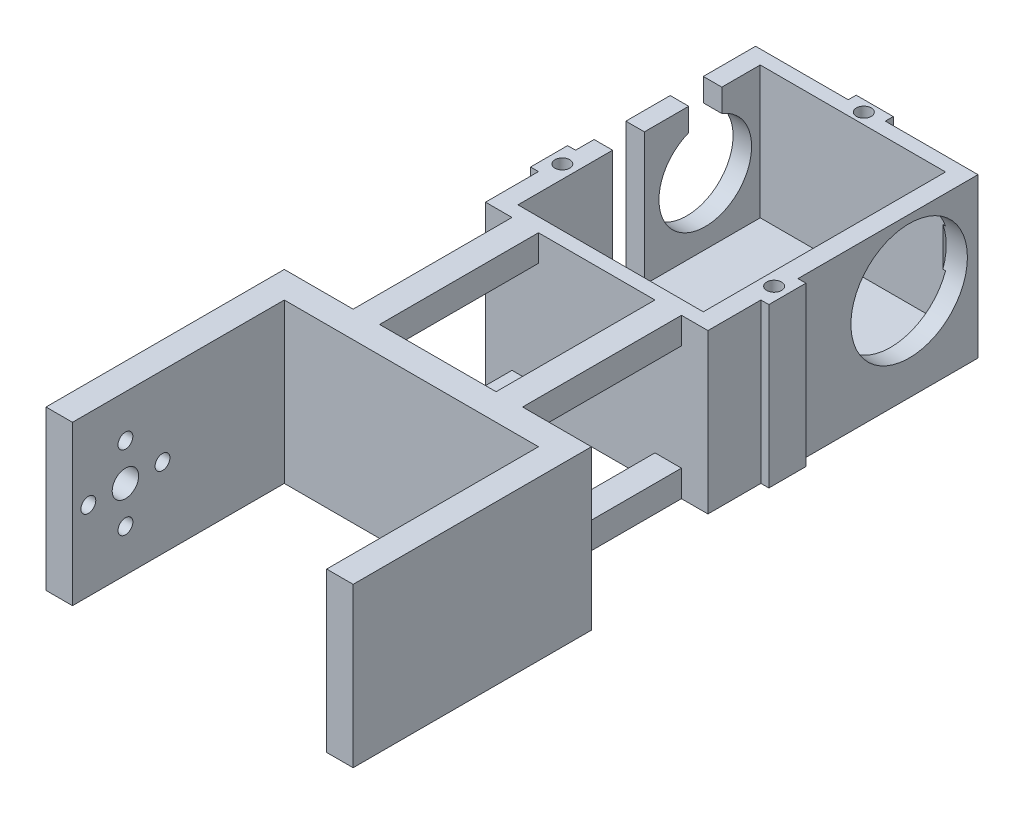
SolidWorks part; units mm, degrees
ref_plane "Front Plane" through (0, 0, 0) normal (0, 0, 1) x (1, 0, 0)
ref_plane "Top Plane" through (0, 0, 0) normal (0, 1, 0) x (1, 0, 0)
ref_plane "Right Plane" through (0, 0, 0) normal (1, 0, 0) x (0, 0, -1)
sketch "Sketch1" plane through (0, 0, 0) normal (0, 1, 0) x (1, 0, 0)
  line L1 (-21, 25.5) -> (21, 25.5)
  line L2 (-21, 25.5) -> (-21, -25.5)
  line L3 (-21, -25.5) -> (21, -25.5)
  line L4 (21, 25.5) -> (21, -25.5)
  line L5 (-11, -25.5) -> (-16, -25.5)
  line L6 (-11, -25.5) -> (-11, -55.5)
  line L7 (-11, -55.5) -> (-16, -55.5)
  line L8 (-16, -25.5) -> (-16, -55.5)
  line L9 (16, -25.5) -> (11, -25.5)
  line L10 (16, -25.5) -> (16, -55.5)
  line L11 (16, -55.5) -> (11, -55.5)
  line L12 (11, -25.5) -> (11, -55.5)
  line L13 (-29, -55.5) -> (29, -55.5)
  line L14 (-29, -55.5) -> (-29, -60.5)
  line L15 (-29, -60.5) -> (29, -60.5)
  line L16 (29, -55.5) -> (29, -60.5)
  line L17 (-24, -60.5) -> (-29, -60.5)
  line L18 (-24, -60.5) -> (-24, -100.5)
  line L19 (-24, -100.5) -> (-29, -100.5)
  line L20 (-29, -60.5) -> (-29, -100.5)
  line L21 (29, -60.5) -> (24, -60.5)
  line L22 (29, -60.5) -> (29, -100.5)
  line L23 (29, -100.5) -> (24, -100.5)
  line L24 (24, -60.5) -> (24, -100.5)
  point P4 (-21, 0)
  point P6 (0, 25.5)
  point P12 (0, -25.5)
  point P21 (0, -55.5)
  dimension "D1" = 42
  dimension "D2" = 51
  dimension "D3" = 5
  dimension "D4" = 30
  dimension "D5" = 5
  dimension "D6" = 5
  dimension "D7" = 5
  dimension "D8" = 58
  dimension "D9" = 40
extrude "Boss-Extrude1" add sketch "Sketch1" along normal blind 5 contours L4 L1 L2 L3 region at (0, 0, 0)
sketch "Sketch3" plane through (0, 5, 0) normal (0, 1, 0) x (1, 0, 0)
  line L1 (-17.5, 22.875) -> (17.5, 22.875)
  line L2 (-17.5, 22.875) -> (-17.5, -22.875)
  line L3 (-17.5, -22.875) -> (17.5, -22.875)
  line L4 (17.5, 22.875) -> (17.5, -22.875)
  line L5 (-21, 25.5) -> (21, 25.5)
  line L6 (-21, 25.5) -> (-21, -25.5)
  line L7 (-21, -25.5) -> (21, -25.5)
  line L8 (21, 25.5) -> (21, -25.5)
  point P4 (-17.5, 0)
  point P6 (0, 22.875)
  dimension "D1" = 35
  dimension "D2" = 45.75
extrude "Boss-Extrude3" add sketch "Sketch3" along normal blind 25
sketch "Sketch4" plane through (-21, 0, 0) normal (-1, 0, 0) x (0, 0, 1)
  line L1 (-25.5, 30) -> (25.5, 30) construction
  line L2 (0, 30) -> (0, 0) construction
  circle A0 centre (-12.5, 17.5) radius 8.75
  dimension "D2" = 17.5
  dimension "D1" = 12.5
  dimension "D3" = 12.5
extrude "Cut-Extrude2" cut sketch "Sketch4" against normal blind 5
sketch "Sketch6" plane through (-17.5, 0, 0) normal (1, 0, 0) x (0, 0, -1)
  line L0 (-25.5, 30) -> (25.5, 30) construction
  line L2 (0, 30) -> (0, 0) construction
  line L4 (9.375, 17.5) -> (9.375, 30)
  line L5 (9.375, 30) -> (15.625, 30)
  line L6 (15.625, 17.5) -> (15.625, 30)
  line L7 (25.5, 0) -> (-25.5, 0) construction
  arc A0 (9.375, 17.5) -> (15.625, 17.5) centre (12.5, 17.5) ccw
  point P11 (12.5, 30)
  dimension "D1" = 6.25
  dimension "D2" = 12.5
  dimension "D3" = 12.5
extrude "Cut-Extrude3" cut sketch "Sketch6" against normal blind 4
sketch "Sketch7" plane through (-21, 0, 0) normal (-1, 0, 0) x (0, 0, 1)
  line L0 (-9.375, 30) -> (25.5, 30) construction
  line L1 (-1, 30) -> (5, 30)
  line L2 (-1, 30) -> (-1, 5)
  line L3 (-1, 5) -> (5, 5)
  line L4 (5, 30) -> (5, 5)
  line L6 (25.5, 30) -> (25.5, 0) construction
  line L7 (-25.5, 0) -> (25.5, 0) construction
  dimension "D1" = 20.5
  dimension "D2" = 5
  dimension "D3" = 6
extrude "Cut-Extrude4" cut sketch "Sketch7" against normal blind 4
sketch "Sketch9" plane through (21, 0, 0) normal (1, 0, 0) x (0, 0, -1)
  line L0 (25.5, 30) -> (25.5, 0) construction
  line L1 (-25.5, 30) -> (25.5, 30) construction
  circle A0 centre (12.5, 17.5) radius 11
  dimension "D2" = 22
  dimension "D1" = 13
  dimension "D3" = 12.5
extrude "Cut-Extrude5" cut sketch "Sketch9" against normal blind 4
sketch "Sketch16" plane through (-21, 0, 0) normal (-1, 0, 0) x (0, 0, 1)
  line L0 (5, 30) -> (25.5, 30) construction
  line L1 (15.5, 30) -> (8.5, 30)
  line L2 (15.5, 30) -> (15.5, 0)
  line L3 (15.5, 0) -> (8.5, 0)
  line L4 (8.5, 30) -> (8.5, 0)
  line L5 (-25.5, 0) -> (25.5, 0) construction
  line L6 (25.5, 30) -> (25.5, 0) construction
  dimension "D1" = 10
  dimension "D2" = 7
extrude "Boss-Extrude5" add sketch "Sketch16" along normal blind 1.5
sketch "Sketch17" plane through (21, 0, 0) normal (1, 0, 0) x (0, 0, -1)
  line L0 (-25.5, 30) -> (25.5, 30) construction
  line L1 (-15.5, 30) -> (-8.5, 30)
  line L2 (-15.5, 30) -> (-15.5, 0)
  line L3 (-15.5, 0) -> (-8.5, 0)
  line L4 (-8.5, 30) -> (-8.5, 0)
  line L5 (25.5, 0) -> (-25.5, 0) construction
  line L6 (-25.5, 30) -> (-25.5, 0) construction
  dimension "D1" = 10
  dimension "D2" = 7
extrude "Boss-Extrude6" add sketch "Sketch17" along normal blind 1.5
sketch "Sketch19" plane through (0, 0, -25.5) normal (0, 0, -1) x (-1, 0, 0)
  line L0 (-21, 30) -> (21, 30) construction
  line L1 (3.5, 30) -> (-3.5, 30)
  line L2 (3.5, 30) -> (3.5, 0)
  line L3 (3.5, 0) -> (-3.5, 0)
  line L4 (-3.5, 30) -> (-3.5, 0)
  line L5 (21, 0) -> (-21, 0) construction
  point P8 (0, 0)
  point P9 (0, 30)
  dimension "D1" = 7
extrude "Boss-Extrude7" add sketch "Sketch19" along normal blind 1.5
sketch "Sketch18" plane through (0, 30, 0) normal (0, 1, 0) x (1, 0, 0)
  line L0 (-22.5, -15.5) -> (-22.5, -8.5) construction
  line L1 (0, -19.5533) -> (0, 11.7982) construction
  line L2 (-3.5, 27) -> (3.5, 27) construction
  line L3 (-22.5, -12) -> (-17.5, -12) construction
  line L4 (-17.5, -5) -> (-17.5, -22.875) construction
  line L5 (0, 27) -> (0, 22.875) construction
  line L6 (17.5, 22.875) -> (-17.5, 22.875) construction
  circle A0 centre (-20, -12) radius 1.4
  circle A1 centre (20, -12) radius 1.4
  circle A2 centre (0, 24.9375) radius 1.4
  point P5 (-22.5, -12)
  point P17 (0, 27)
  point P21 (-20, -12)
  point P26 (0, 24.9375)
  dimension "D1" = 2.8
extrude "Cut-Extrude7" cut sketch "Sketch18" against normal blind 6
extrude "Boss-Extrude8" add sketch "Sketch1<3>" along normal blind 30 contours L3 L8 L7 L6 | L3 L12 L11 L10 | L16 L13 L11 L7 L14 L15 | L15 L24 L23 L22 | L15 L20 L19 L18
sketch "Sketch1<3>" plane through (0, 0, 0) normal (0, 1, 0) x (1, 0, 0) same geometry as "Sketch1"
sketch "Sketch21" plane through (24, 0, 0) normal (-1, 0, 0) x (0, 0, 1)
  line L0 (100.5, 30) -> (100.5, 0) construction
  circle A0 centre (90.5, 15) radius 2.95
  point P6 (100.5, 15)
  dimension "D1" = 5.9
  dimension "D2" = 10
extrude "Boss-Extrude9" add sketch "Sketch21" along normal blind 4
sketch "Sketch24" plane through (-16, 0, 0) normal (-1, 0, 0) x (0, 0, 1)
  line L0 (25.5, 30) -> (25.5, 0) construction
  line L1 (25.5, 25) -> (55.5, 25)
  line L2 (25.5, 25) -> (25.5, 5)
  line L3 (25.5, 5) -> (55.5, 5)
  line L4 (55.5, 25) -> (55.5, 5)
  line L5 (55.5, 30) -> (55.5, 0) construction
  point P8 (25.5, 15)
  point P9 (25.5, 15)
  dimension "D1" = 20
extrude "Cut-Extrude8" cut sketch "Sketch24" against normal blind 32
sketch "Sketch25" plane through (-29, 0, 0) normal (-1, 0, 0) x (0, 0, 1)
  line L0 (90.5, 22) -> (90.5, 15) construction
  line L1 (90.5, 15) -> (83.5, 15) construction
  circle A0 centre (90.5, 15) radius 2.5
  circle A1 centre (90.5, 15) radius 2.95 construction
  circle A2 centre (90.5, 22) radius 1.4
  circle A3 centre (83.5, 15) radius 1.4
  circle A4 centre (90.5, 8) radius 1.4
  circle A5 centre (97.5, 15) radius 1.4
  dimension "D1" = 5
  dimension "D3" = 2.8
  dimension "D2" = 7
extrude "Cut-Extrude9" cut sketch "Sketch25" against normal blind 5
